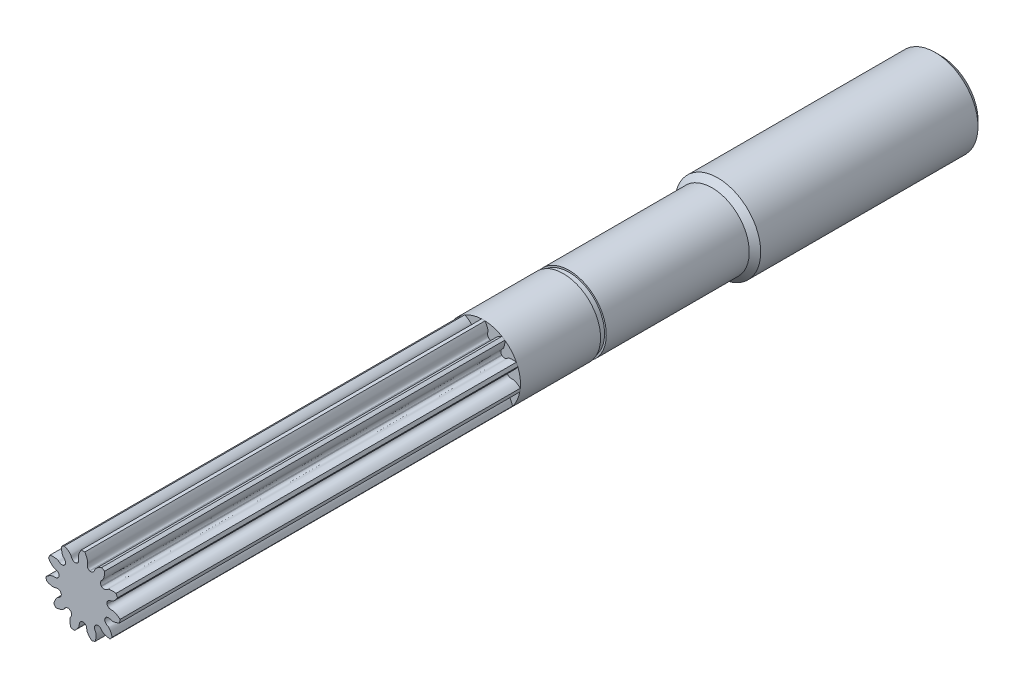
SolidWorks part; units mm, degrees
ref_plane "Спереди" through (0, 0, 0) normal (0, 0, 1) x (1, 0, 0)
ref_plane "Сверху" through (0, 0, 0) normal (0, 1, 0) x (1, 0, 0)
ref_plane "Справа" through (0, 0, 0) normal (1, 0, 0) x (0, 0, -1)
other "Configuration Table"
sketch "Эскиз1" plane through (0, 0, 0) normal (0, 0, 1) x (1, 0, 0)
  line L0 (0, 4.2505) -> (0, 6.5001) construction
  arc A6 (0.303, 6.493) -> (-0.303, 6.493) centre (0, 0) ccw
  arc A8 (3.7653, 5.2984) -> (3.2555, 5.6261) centre (0, 0) ccw
  arc A9 (6.0321, 2.4217) -> (5.7804, 2.9729) centre (0, 0) ccw
  arc A10 (6.3838, -1.224) -> (6.47, -0.6241) centre (0, 0) ccw
  arc A11 (4.7087, -4.481) -> (5.1055, -4.023) centre (0, 0) ccw
  arc A12 (1.5386, -6.3154) -> (2.12, -6.1446) centre (0, 0) ccw
  arc A13 (-2.12, -6.1446) -> (-1.5386, -6.3154) centre (0, 0) ccw
  arc A14 (-5.1055, -4.023) -> (-4.7087, -4.481) centre (0, 0) ccw
  arc A15 (-6.47, -0.6241) -> (-6.3838, -1.224) centre (0, 0) ccw
  arc A16 (-5.7804, 2.9729) -> (-6.0321, 2.4217) centre (0, 0) ccw
  arc A17 (-3.2555, 5.6261) -> (-3.7653, 5.2984) centre (0, 0) ccw
  arc A18 (-4.1999, 0.6538) -> (-4.214, 0.5559) centre (0, 0) ccw
  arc A19 (-3.1797, 2.8207) -> (-3.2445, 2.746) centre (0, 0) ccw
  arc A20 (-1.15, 4.092) -> (-1.2449, 4.0641) centre (0, 0) ccw
  arc A21 (1.2449, 4.0641) -> (1.15, 4.092) centre (0, 0) ccw
  arc A22 (3.2445, 2.746) -> (3.1797, 2.8207) centre (0, 0) ccw
  arc A23 (4.214, 0.5559) -> (4.1999, 0.6538) centre (0, 0) ccw
  arc A24 (3.8456, -1.8106) -> (3.8867, -1.7206) centre (0, 0) ccw
  arc A25 (2.2563, -3.6023) -> (2.3394, -3.5488) centre (0, 0) ccw
  arc A26 (-0.0494, -4.2502) -> (0.0494, -4.2502) centre (0, 0) ccw
  arc A27 (-2.3394, -3.5488) -> (-2.2563, -3.6023) centre (0, 0) ccw
  arc A28 (-3.8867, -1.7206) -> (-3.8456, -1.8106) centre (0, 0) ccw
  spline S0 degree 3 poles (0.303, 6.493) (0.3466, 6.4296) (0.4149, 6.3229) (0.5038, 6.1711) (0.5716, 6.0406) (0.6313, 5.9095) (0.6852, 5.7791) (0.7296, 5.6484) (0.7674, 5.5183) (0.798, 5.3728) (0.8278, 5.1961) (0.7682, 4.9723) (0.7367, 4.7556) (0.754, 4.5684) (0.7852, 4.4471) (0.829, 4.3517) (0.8776, 4.2755) (0.9328, 4.2146) (1.0177, 4.1438) (1.0937, 4.1064) (1.15, 4.092) knots 0 0 0 0 0.085617 0.14097 0.195721 0.24917 0.301247 0.352629 0.402768 0.451734 0.518548 0.599046 0.705842 0.760988 0.807057 0.844573 0.877292 0.907236 0.935686 1 1 1 1
  spline S1 degree 3 poles (-0.303, 6.493) (-0.3466, 6.4296) (-0.4149, 6.3229) (-0.5038, 6.1711) (-0.5716, 6.0406) (-0.6313, 5.9095) (-0.6852, 5.7791) (-0.7296, 5.6484) (-0.7674, 5.5183) (-0.798, 5.3728) (-0.8278, 5.1961) (-0.7682, 4.9723) (-0.7367, 4.7556) (-0.754, 4.5684) (-0.7852, 4.4471) (-0.829, 4.3517) (-0.8776, 4.2755) (-0.9328, 4.2146) (-1.0177, 4.1438) (-1.0937, 4.1064) (-1.15, 4.092) knots 0 0 0 0 0.085617 0.14097 0.195721 0.24917 0.301247 0.352629 0.402768 0.451734 0.518548 0.599046 0.705842 0.760988 0.807057 0.844573 0.877292 0.907236 0.935686 1 1 1 1
  spline S2 degree 3 poles (3.2555, 5.6261) (3.1845, 5.5963) (3.0694, 5.5435) (2.9125, 5.4638) (2.7849, 5.3907) (2.6639, 5.3126) (2.548, 5.2321) (2.4399, 5.1462) (2.3379, 5.0572) (2.2335, 4.9513) (2.1128, 4.8187) (2.042, 4.5983) (1.9513, 4.399) (1.8356, 4.2508) (1.7437, 4.1657) (1.6553, 4.1091) (1.5733, 4.0713) (1.4939, 4.0498) (1.3841, 4.0362) (1.3, 4.0458) (1.2449, 4.0641) knots 0 0 0 0 0.085617 0.14097 0.195721 0.24917 0.301247 0.352629 0.402768 0.451734 0.518548 0.599046 0.705842 0.760988 0.807057 0.844573 0.877292 0.907236 0.935686 1 1 1 1
  spline S3 degree 3 poles (3.7653, 5.2984) (3.7677, 5.2215) (3.7674, 5.0948) (3.7602, 4.9191) (3.7467, 4.7726) (3.7259, 4.6301) (3.7008, 4.4913) (3.6676, 4.3573) (3.629, 4.2274) (3.5761, 4.0885) (3.5056, 3.9237) (3.3345, 3.7676) (3.1908, 3.6024) (3.1041, 3.4356) (3.0649, 3.3166) (3.0502, 3.2127) (3.0498, 3.1224) (3.0633, 3.0412) (3.0965, 2.9357) (3.1402, 2.8632) (3.1797, 2.8207) knots 0 0 0 0 0.085617 0.14097 0.195721 0.24917 0.301247 0.352629 0.402768 0.451734 0.518548 0.599046 0.705842 0.760988 0.807057 0.844573 0.877292 0.907236 0.935686 1 1 1 1
  spline S4 degree 3 poles (5.7804, 2.9729) (5.7046, 2.9862) (5.5791, 3.004) (5.4041, 3.0219) (5.2573, 3.0293) (5.1132, 3.0291) (4.9722, 3.024) (4.8349, 3.0101) (4.7009, 2.9904) (4.5558, 2.9578) (4.3826, 2.9115) (4.2038, 2.7644) (4.0198, 2.6457) (3.8424, 2.5836) (3.719, 2.5617) (3.6141, 2.5619) (3.5246, 2.5744) (3.4462, 2.5993) (3.3465, 2.6472) (3.281, 2.7007) (3.2445, 2.746) knots 0 0 0 0 0.085617 0.14097 0.195721 0.24917 0.301247 0.352629 0.402768 0.451734 0.518548 0.599046 0.705842 0.760988 0.807057 0.844573 0.877292 0.907236 0.935686 1 1 1 1
  spline S5 degree 3 poles (6.0321, 2.4217) (5.9925, 2.3557) (5.9238, 2.2492) (5.8227, 2.1053) (5.7322, 1.9894) (5.6377, 1.8807) (5.5415, 1.7775) (5.4411, 1.6827) (5.3384, 1.5943) (5.2188, 1.5061) (5.0704, 1.4055) (4.8421, 1.3668) (4.6319, 1.3054) (4.4688, 1.212) (4.3714, 1.1331) (4.3029, 1.0537) (4.2537, 0.9778) (4.2212, 0.9023) (4.1921, 0.7956) (4.1897, 0.711) (4.1999, 0.6538) knots 0 0 0 0 0.085617 0.14097 0.195721 0.24917 0.301247 0.352629 0.402768 0.451734 0.518548 0.599046 0.705842 0.760988 0.807057 0.844573 0.877292 0.907236 0.935686 1 1 1 1
  spline S6 degree 3 poles (6.47, -0.6241) (6.4135, -0.572) (6.3176, -0.4892) (6.18, -0.3795) (6.0605, -0.2938) (5.9391, -0.2162) (5.8178, -0.1442) (5.6948, -0.0816) (5.5714, -0.0258) (5.4317, 0.0252) (5.261, 0.0799) (5.031, 0.0528) (4.812, 0.0524) (4.6292, 0.0961) (4.5136, 0.1444) (4.4254, 0.2013) (4.3569, 0.2602) (4.3044, 0.3235) (4.2465, 0.4177) (4.2203, 0.4982) (4.214, 0.5559) knots 0 0 0 0 0.085617 0.14097 0.195721 0.24917 0.301247 0.352629 0.402768 0.451734 0.518548 0.599046 0.705842 0.760988 0.807057 0.844573 0.877292 0.907236 0.935686 1 1 1 1
  spline S7 degree 3 poles (6.3838, -1.224) (6.3148, -1.2581) (6.1995, -1.3105) (6.0366, -1.3769) (5.8978, -1.4255) (5.7595, -1.4658) (5.6228, -1.5007) (5.4871, -1.5261) (5.3529, -1.5449) (5.2046, -1.5545) (5.0254, -1.5588) (4.8124, -1.468) (4.6023, -1.406) (4.4146, -1.3964) (4.2901, -1.4101) (4.1895, -1.4399) (4.1071, -1.4771) (4.0389, -1.5231) (3.9568, -1.5971) (3.909, -1.667) (3.8867, -1.7206) knots 0 0 0 0 0.085617 0.14097 0.195721 0.24917 0.301247 0.352629 0.402768 0.451734 0.518548 0.599046 0.705842 0.760988 0.807057 0.844573 0.877292 0.907236 0.935686 1 1 1 1
  spline S8 degree 3 poles (5.1055, -4.023) (5.0861, -3.9486) (5.0502, -3.827) (4.9937, -3.6604) (4.9395, -3.5237) (4.8795, -3.3928) (4.8163, -3.2667) (4.7466, -3.1475) (4.673, -3.0338) (4.5831, -2.9154) (4.469, -2.7771) (4.2609, -2.6756) (4.0765, -2.5575) (3.9463, -2.4219) (3.8751, -2.3188) (3.8317, -2.2233) (3.8059, -2.1366) (3.796, -2.055) (3.7981, -1.9445) (3.8196, -1.8626) (3.8456, -1.8106) knots 0 0 0 0 0.085617 0.14097 0.195721 0.24917 0.301247 0.352629 0.402768 0.451734 0.518548 0.599046 0.705842 0.760988 0.807057 0.844573 0.877292 0.907236 0.935686 1 1 1 1
  spline S9 degree 3 poles (4.7087, -4.481) (4.6322, -4.4724) (4.5068, -4.4542) (4.3339, -4.422) (4.1908, -4.3878) (4.0527, -4.3469) (3.9189, -4.3023) (3.791, -4.2503) (3.6679, -4.1937) (3.538, -4.1215) (3.3848, -4.0283) (3.2547, -3.8367) (3.1116, -3.671) (2.9588, -3.5615) (2.8467, -3.5057) (2.7459, -3.4763) (2.6565, -3.4631) (2.5743, -3.4649) (2.4652, -3.4828) (2.3872, -3.5157) (2.3394, -3.5488) knots 0 0 0 0 0.085617 0.14097 0.195721 0.24917 0.301247 0.352629 0.402768 0.451734 0.518548 0.599046 0.705842 0.760988 0.807057 0.844573 0.877292 0.907236 0.935686 1 1 1 1
  spline S10 degree 3 poles (2.12, -6.1446) (2.144, -6.0715) (2.1795, -5.9499) (2.222, -5.7792) (2.2503, -5.6349) (2.2706, -5.4922) (2.2856, -5.352) (2.2914, -5.214) (2.291, -5.0786) (2.2793, -4.9304) (2.2582, -4.7524) (2.138, -4.5545) (2.0467, -4.3554) (2.0105, -4.1709) (2.0063, -4.0457) (2.0215, -3.9419) (2.0466, -3.8551) (2.0824, -3.7811) (2.144, -3.6892) (2.2063, -3.6319) (2.2563, -3.6023) knots 0 0 0 0 0.085617 0.14097 0.195721 0.24917 0.301247 0.352629 0.402768 0.451734 0.518548 0.599046 0.705842 0.760988 0.807057 0.844573 0.877292 0.907236 0.935686 1 1 1 1
  spline S11 degree 3 poles (1.5386, -6.3154) (1.4789, -6.2668) (1.3833, -6.1836) (1.2552, -6.0631) (1.1533, -5.957) (1.0592, -5.8479) (0.9707, -5.738) (0.8913, -5.6252) (0.8184, -5.511) (0.7481, -5.38) (0.6696, -5.2188) (0.6638, -4.9873) (0.6329, -4.7705) (0.5636, -4.5958) (0.4995, -4.4882) (0.4306, -4.409) (0.3625, -4.3496) (0.2924, -4.3067) (0.1909, -4.2627) (0.1075, -4.2482) (0.0494, -4.2502) knots 0 0 0 0 0.085617 0.14097 0.195721 0.24917 0.301247 0.352629 0.402768 0.451734 0.518548 0.599046 0.705842 0.760988 0.807057 0.844573 0.877292 0.907236 0.935686 1 1 1 1
  spline S12 degree 3 poles (-1.5386, -6.3154) (-1.4789, -6.2668) (-1.3833, -6.1836) (-1.2552, -6.0631) (-1.1533, -5.957) (-1.0592, -5.8479) (-0.9707, -5.738) (-0.8913, -5.6252) (-0.8184, -5.511) (-0.7481, -5.38) (-0.6696, -5.2188) (-0.6638, -4.9873) (-0.6329, -4.7705) (-0.5636, -4.5958) (-0.4995, -4.4882) (-0.4306, -4.409) (-0.3625, -4.3496) (-0.2924, -4.3067) (-0.1909, -4.2627) (-0.1075, -4.2482) (-0.0494, -4.2502) knots 0 0 0 0 0.085617 0.14097 0.195721 0.24917 0.301247 0.352629 0.402768 0.451734 0.518548 0.599046 0.705842 0.760988 0.807057 0.844573 0.877292 0.907236 0.935686 1 1 1 1
  spline S13 degree 3 poles (-2.12, -6.1446) (-2.144, -6.0715) (-2.1795, -5.9499) (-2.222, -5.7792) (-2.2503, -5.6349) (-2.2706, -5.4922) (-2.2856, -5.352) (-2.2914, -5.214) (-2.291, -5.0786) (-2.2793, -4.9304) (-2.2582, -4.7524) (-2.138, -4.5545) (-2.0467, -4.3554) (-2.0105, -4.1709) (-2.0063, -4.0457) (-2.0215, -3.9419) (-2.0466, -3.8551) (-2.0824, -3.7811) (-2.144, -3.6892) (-2.2063, -3.6319) (-2.2563, -3.6023) knots 0 0 0 0 0.085617 0.14097 0.195721 0.24917 0.301247 0.352629 0.402768 0.451734 0.518548 0.599046 0.705842 0.760988 0.807057 0.844573 0.877292 0.907236 0.935686 1 1 1 1
  spline S14 degree 3 poles (-4.7087, -4.481) (-4.6322, -4.4724) (-4.5068, -4.4542) (-4.3339, -4.422) (-4.1908, -4.3878) (-4.0527, -4.3469) (-3.9189, -4.3023) (-3.791, -4.2503) (-3.6679, -4.1937) (-3.538, -4.1215) (-3.3848, -4.0283) (-3.2547, -3.8367) (-3.1116, -3.671) (-2.9588, -3.5615) (-2.8467, -3.5057) (-2.7459, -3.4763) (-2.6565, -3.4631) (-2.5743, -3.4649) (-2.4652, -3.4828) (-2.3872, -3.5157) (-2.3394, -3.5488) knots 0 0 0 0 0.085617 0.14097 0.195721 0.24917 0.301247 0.352629 0.402768 0.451734 0.518548 0.599046 0.705842 0.760988 0.807057 0.844573 0.877292 0.907236 0.935686 1 1 1 1
  spline S15 degree 3 poles (-5.1055, -4.023) (-5.0861, -3.9486) (-5.0502, -3.827) (-4.9937, -3.6604) (-4.9395, -3.5237) (-4.8795, -3.3928) (-4.8163, -3.2667) (-4.7466, -3.1475) (-4.673, -3.0338) (-4.5831, -2.9154) (-4.469, -2.7771) (-4.2609, -2.6756) (-4.0765, -2.5575) (-3.9463, -2.4219) (-3.8751, -2.3188) (-3.8317, -2.2233) (-3.8059, -2.1366) (-3.796, -2.055) (-3.7981, -1.9445) (-3.8196, -1.8626) (-3.8456, -1.8106) knots 0 0 0 0 0.085617 0.14097 0.195721 0.24917 0.301247 0.352629 0.402768 0.451734 0.518548 0.599046 0.705842 0.760988 0.807057 0.844573 0.877292 0.907236 0.935686 1 1 1 1
  spline S16 degree 3 poles (-6.3838, -1.224) (-6.3148, -1.2581) (-6.1995, -1.3105) (-6.0366, -1.3769) (-5.8978, -1.4255) (-5.7595, -1.4658) (-5.6228, -1.5007) (-5.4871, -1.5261) (-5.3529, -1.5449) (-5.2046, -1.5545) (-5.0254, -1.5588) (-4.8124, -1.468) (-4.6023, -1.406) (-4.4146, -1.3964) (-4.2901, -1.4101) (-4.1895, -1.4399) (-4.1071, -1.4771) (-4.0389, -1.5231) (-3.9568, -1.5971) (-3.909, -1.667) (-3.8867, -1.7206) knots 0 0 0 0 0.085617 0.14097 0.195721 0.24917 0.301247 0.352629 0.402768 0.451734 0.518548 0.599046 0.705842 0.760988 0.807057 0.844573 0.877292 0.907236 0.935686 1 1 1 1
  spline S17 degree 3 poles (-6.47, -0.6241) (-6.4135, -0.572) (-6.3176, -0.4892) (-6.18, -0.3795) (-6.0605, -0.2938) (-5.9391, -0.2162) (-5.8178, -0.1442) (-5.6948, -0.0816) (-5.5714, -0.0258) (-5.4317, 0.0252) (-5.261, 0.0799) (-5.031, 0.0528) (-4.812, 0.0524) (-4.6292, 0.0961) (-4.5136, 0.1444) (-4.4254, 0.2013) (-4.3569, 0.2602) (-4.3044, 0.3235) (-4.2465, 0.4177) (-4.2203, 0.4982) (-4.214, 0.5559) knots 0 0 0 0 0.085617 0.14097 0.195721 0.24917 0.301247 0.352629 0.402768 0.451734 0.518548 0.599046 0.705842 0.760988 0.807057 0.844573 0.877292 0.907236 0.935686 1 1 1 1
  spline S18 degree 3 poles (-6.0321, 2.4217) (-5.9925, 2.3557) (-5.9238, 2.2492) (-5.8227, 2.1053) (-5.7322, 1.9894) (-5.6377, 1.8807) (-5.5415, 1.7775) (-5.4411, 1.6827) (-5.3384, 1.5943) (-5.2188, 1.5061) (-5.0704, 1.4055) (-4.8421, 1.3668) (-4.6319, 1.3054) (-4.4688, 1.212) (-4.3714, 1.1331) (-4.3029, 1.0537) (-4.2537, 0.9778) (-4.2212, 0.9023) (-4.1921, 0.7956) (-4.1897, 0.711) (-4.1999, 0.6538) knots 0 0 0 0 0.085617 0.14097 0.195721 0.24917 0.301247 0.352629 0.402768 0.451734 0.518548 0.599046 0.705842 0.760988 0.807057 0.844573 0.877292 0.907236 0.935686 1 1 1 1
  spline S19 degree 3 poles (-5.7804, 2.9729) (-5.7046, 2.9862) (-5.5791, 3.004) (-5.4041, 3.0219) (-5.2573, 3.0293) (-5.1132, 3.0291) (-4.9722, 3.024) (-4.8349, 3.0101) (-4.7009, 2.9904) (-4.5558, 2.9578) (-4.3826, 2.9115) (-4.2038, 2.7644) (-4.0198, 2.6457) (-3.8424, 2.5836) (-3.719, 2.5617) (-3.6141, 2.5619) (-3.5246, 2.5744) (-3.4462, 2.5993) (-3.3465, 2.6472) (-3.281, 2.7007) (-3.2445, 2.746) knots 0 0 0 0 0.085617 0.14097 0.195721 0.24917 0.301247 0.352629 0.402768 0.451734 0.518548 0.599046 0.705842 0.760988 0.807057 0.844573 0.877292 0.907236 0.935686 1 1 1 1
  spline S20 degree 3 poles (-3.7653, 5.2984) (-3.7677, 5.2215) (-3.7674, 5.0948) (-3.7602, 4.9191) (-3.7467, 4.7726) (-3.7259, 4.6301) (-3.7008, 4.4913) (-3.6676, 4.3573) (-3.629, 4.2274) (-3.5761, 4.0885) (-3.5056, 3.9237) (-3.3345, 3.7676) (-3.1908, 3.6024) (-3.1041, 3.4356) (-3.0649, 3.3166) (-3.0502, 3.2127) (-3.0498, 3.1224) (-3.0633, 3.0412) (-3.0965, 2.9357) (-3.1402, 2.8632) (-3.1797, 2.8207) knots 0 0 0 0 0.085617 0.14097 0.195721 0.24917 0.301247 0.352629 0.402768 0.451734 0.518548 0.599046 0.705842 0.760988 0.807057 0.844573 0.877292 0.907236 0.935686 1 1 1 1
  spline S21 degree 3 poles (-3.2555, 5.6261) (-3.1845, 5.5963) (-3.0694, 5.5435) (-2.9125, 5.4638) (-2.7849, 5.3907) (-2.6639, 5.3126) (-2.548, 5.2321) (-2.4399, 5.1462) (-2.3379, 5.0572) (-2.2335, 4.9513) (-2.1128, 4.8187) (-2.042, 4.5983) (-1.9513, 4.399) (-1.8356, 4.2508) (-1.7437, 4.1657) (-1.6553, 4.1091) (-1.5733, 4.0713) (-1.4939, 4.0498) (-1.3841, 4.0362) (-1.3, 4.0458) (-1.2449, 4.0641) knots 0 0 0 0 0.085617 0.14097 0.195721 0.24917 0.301247 0.352629 0.402768 0.451734 0.518548 0.599046 0.705842 0.760988 0.807057 0.844573 0.877292 0.907236 0.935686 1 1 1 1
  point P469 (0, 0)
  point P490 (0, 0)
  dimension "D1" = 11
  dimension "D2" = 11
extrude "Бобышка-Вытянуть1" add sketch "Эскиз1" along normal blind 70
sketch "Эскиз3" plane through (0, 0, 0) normal (1, 0, 0) x (0, 0, -1)
  line L1 (0, 50) -> (0, -50) construction
  line L2 (40, 6.5) -> (40, 7.5)
  line L3 (40, 7.5) -> (80, 7.5)
  line L4 (80, 7.5) -> (80, 0)
  line L5 (80, 0) -> (0, 0)
  line L6 (0, 0) -> (0, 6.5)
  line L7 (0, 6.5) -> (14, 6.5)
  line L8 (14, 6.5) -> (14, 6.2)
  line L9 (14, 6.2) -> (15, 6.2)
  line L10 (15, 6.2) -> (15, 6.5)
  line L11 (15, 6.5) -> (40, 6.5)
  dimension "D1" = 80
  dimension "D2" = 25
  dimension "D3" = 40
  dimension "D4" = 7.5
  dimension "D5" = 1
  dimension "D6" = 0.3
  dimension "D7" = 6.5
  dimension "D8" = 6.5
revolve "Повернуть1" add sketch "Эскиз3" angle 360 about L5
chamfer "Фаска1" distance 1 angle 45 2 edges at (0, 7.5, -40) (0, 7.5, -80)
sketch "Эскиз5" plane through (0, 0, 0) normal (0, 0, 1) x (1, 0, 0)
  circle A0 centre (3.0067, 10.24) radius 4.6207
